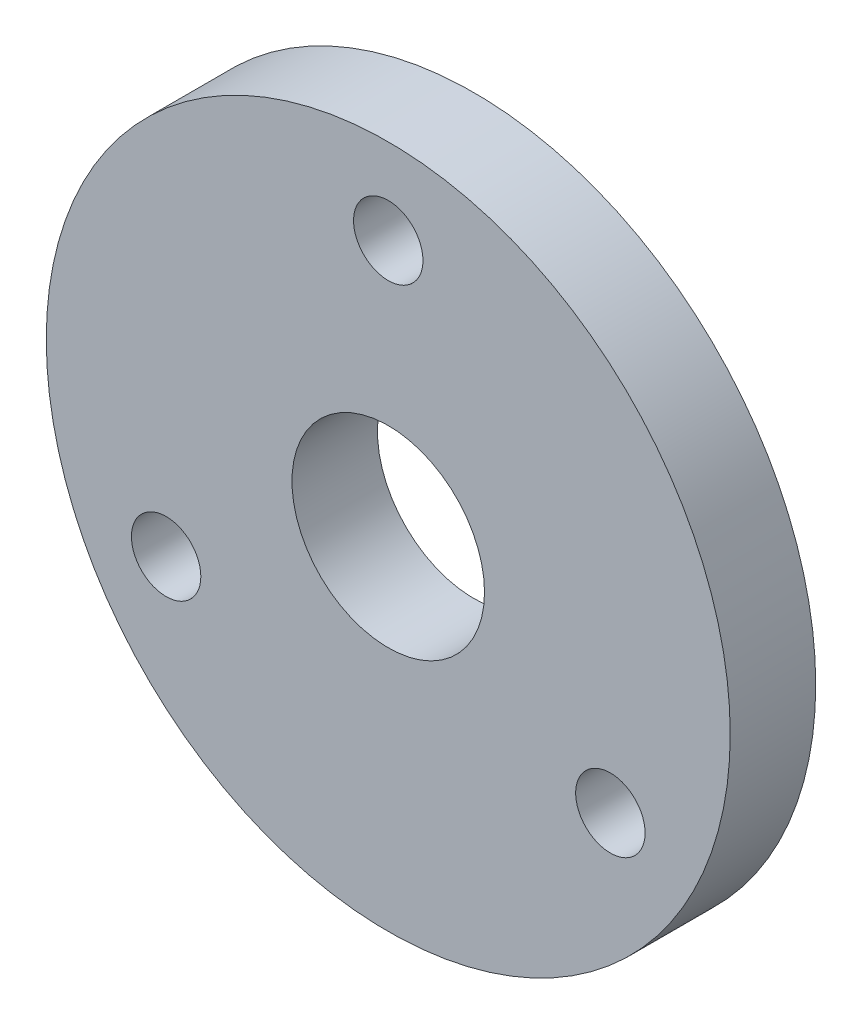
SolidWorks part; units mm, degrees
ref_plane "Front Plane" through (0, 0, 0) normal (0, 0, 1) x (1, 0, 0)
ref_plane "Top Plane" through (0, 0, 0) normal (0, 1, 0) x (1, 0, 0)
ref_plane "Right Plane" through (0, 0, 0) normal (1, 0, 0) x (0, 0, -1)
sketch "Sketch1" plane through (0, 0, 0) normal (0, 0, 1) x (1, 0, 0)
  circle A0 centre (0, 0) radius 25.4
  circle A1 centre (0, 0) radius 7.1501
  circle A2 centre (0, 0) radius 19.05
  circle A3 centre (0, 19.05) radius 2.5781
  circle A4 centre (16.4978, -9.525) radius 2.5781
  circle A5 centre (-16.4978, -9.525) radius 2.5781
  point P14 (0, 0)
  dimension "D1" = 50.8
  dimension "D2" = 14.3002
  dimension "D3" = 38.1
  dimension "D4" = 5.1562
  dimension "D5" = 3
extrude "Boss-Extrude1" add sketch "Sketch1" along normal blind 6.35 contours A0
extrude "Cut-Extrude1" cut sketch "Sketch1<3>" along normal blind 6.35 contours A3 | A5 | A4
sketch "Sketch1<3>" plane through (0, 0, 0) normal (0, 0, 1) x (1, 0, 0) same geometry as "Sketch1"
extrude "Cut-Extrude2" cut sketch "Sketch1<5>" along normal blind 6.35 contours A1 region at (0, 0, 0)
sketch "Sketch1<5>" plane through (0, 0, 0) normal (0, 0, 1) x (1, 0, 0) same geometry as "Sketch1"
